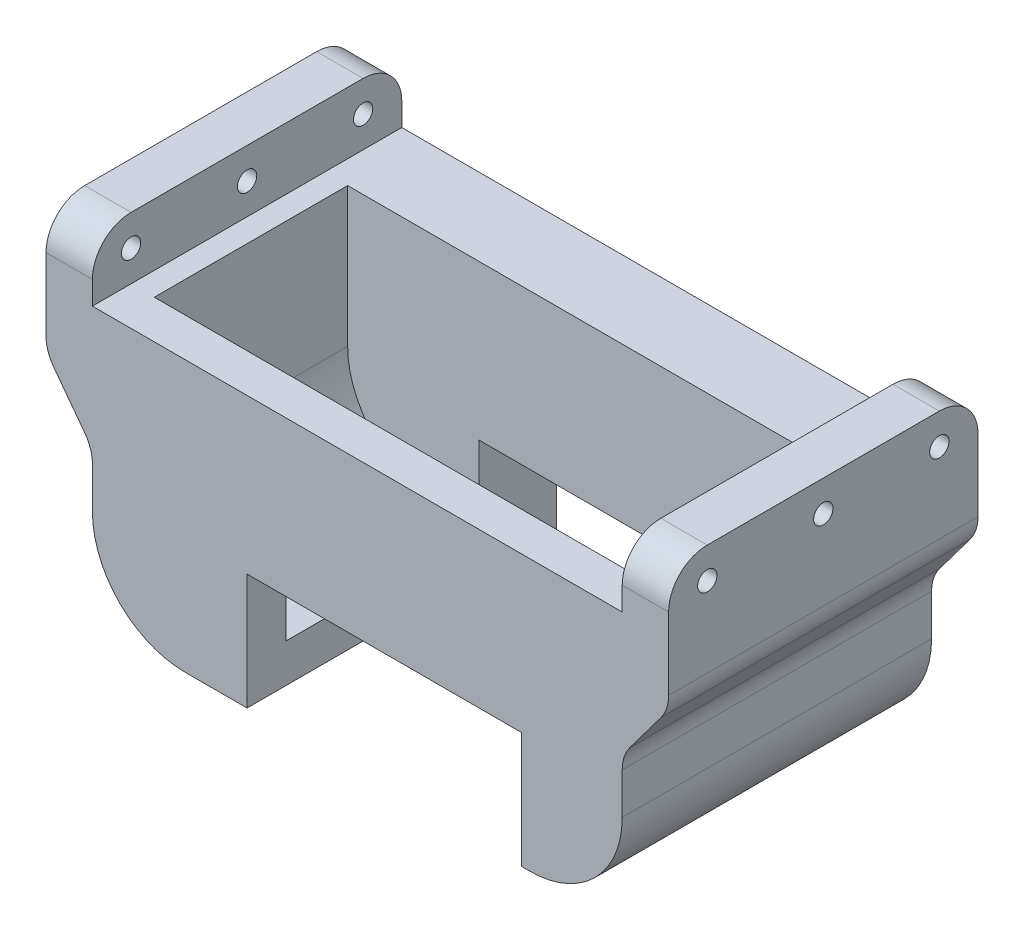
SolidWorks part; units mm, degrees
ref_plane "Front Plane" through (0, 0, 0) normal (0, 0, 1) x (1, 0, 0)
ref_plane "Top Plane" through (0, 0, 0) normal (0, 1, 0) x (1, 0, 0)
ref_plane "Right Plane" through (0, 0, 0) normal (1, 0, 0) x (0, 0, -1)
sketch "Sketch1" plane through (0, 0, 0) normal (0, 0, 1) x (1, 0, 0)
  line L0 (-34.25, 0) -> (34.25, 0)
  line L1 (-34.25, 0) -> (-34.25, -35)
  line L2 (34.25, 0) -> (34.25, -35)
  line L3 (-34.25, -35) -> (-14.25, -35)
  line L4 (34.25, -35) -> (21.25, -35)
  line L5 (-14.25, -35) -> (-14.25, -20)
  line L6 (-14.25, -20) -> (21.25, -20)
  line L7 (21.25, -20) -> (21.25, -35)
  line L8 (-34.25, 0) -> (-34.25, 8)
  line L9 (-34.25, 8) -> (-40.25, 8)
  line L10 (-40.25, 8) -> (-40.25, -8)
  line L11 (34.25, 0) -> (34.25, 8)
  line L12 (34.25, 8) -> (40.25, 8)
  line L13 (40.25, 8) -> (40.25, -8)
  line L14 (-40.25, -8) -> (-34.25, -16)
  line L15 (40.25, -8) -> (34.25, -16)
  point P0 (-37.25, 8)
  point P4 (0, 0)
  dimension "D1" = 68.5
  dimension "D2" = 35
  dimension "D3" = 35
  dimension "D4" = 20
  dimension "D5" = 13
  dimension "D6" = 20
  dimension "D7" = 8
  dimension "D8" = 8
  dimension "D9" = 6
  dimension "D10" = 6
  dimension "D11" = 8
  dimension "D12" = 8
  dimension "D13" = 8
  dimension "D14" = 8
extrude "Boss-Extrude1" add sketch "Sketch1" along normal blind 40 contours L6 L7 L4 L2 L0 L1 L3 L5 | L10 L14 L1 L8 L9 | L15 L13 L12 L11 L2 region at (-0.9993, -14.6448, 0) region at (-37.05, -2.1333, 0) region at (37.05, -2.1333, 0)
sketch "Sketch2" plane through (0, 0, 0) normal (0, 1, 0) x (1, 0, 0)
  line L0 (-14.25, -40) -> (-14.25, 0) construction
  line L1 (-14.25, -35) -> (21.25, -35)
  line L2 (-14.25, -35) -> (-14.25, -10)
  line L3 (-14.25, -10) -> (21.25, -10)
  line L4 (21.25, -35) -> (21.25, -10)
  line L5 (21.25, -40) -> (21.25, 0) construction
  line L9 (-34.25, -40) -> (34.25, -40) construction
  line L10 (-34.25, 0) -> (34.25, 0) construction
  dimension "D1" = 5
  dimension "D2" = 10
extrude "Cut-Extrude1" cut sketch "Sketch2" against normal blind 40
sketch "Sketch3" plane through (0, 0, 0) normal (1, 0, 0) x (0, 0, -1)
  line L0 (-40, 8) -> (-40, -8) construction
  line L1 (-40, 8) -> (0, 8) construction
  line L2 (0, 8) -> (0, -8) construction
  circle A0 centre (-35, 4) radius 1.25
  circle A1 centre (-5, 4) radius 1.25
  circle A2 centre (-20, 4) radius 1.25
  dimension "D1" = 2.5
  dimension "D5" = 2.5
  dimension "D8" = 2.5
  dimension "D2" = 5
  dimension "D3" = 4
  dimension "D4" = 5
  dimension "D6" = 4
  dimension "D7" = 4
  dimension "D9" = 15
extrude "Cut-Extrude2" cut sketch "Sketch3" against normal through all and the other way through all
fillet "Fillet2" radius 5 8 edges at (-34.25, -16, 20) (-40.25, -8, 20) (40.25, -8, 20) (34.25, -16, 20) (37.25, 8, 0) (-37.25, 8, 0) (37.25, 8, 40) (-37.25, 8, 40)
chamfer "Chamfer1" distance 5 angle 45 1 edges at (21.25, -27.5, 0)
sketch "Sketch4" plane through (0, 0, 0) normal (0, 1, 0) x (1, 0, 0)
  line L0 (-14.25, -35) -> (21.25, -35) construction
  line L1 (-14.25, -10) -> (-31.25, -10)
  line L2 (-14.25, -10) -> (-14.25, -35)
  line L3 (-14.25, -35) -> (-31.25, -35)
  line L4 (-31.25, -10) -> (-31.25, -35)
  line L5 (21.25, -10) -> (31.25, -10)
  line L6 (21.25, -10) -> (21.25, -35)
  line L7 (21.25, -35) -> (31.25, -35)
  line L8 (31.25, -10) -> (31.25, -35)
  line L9 (21.25, -35) -> (21.25, -10) construction
  line L10 (34.25, -40) -> (34.25, 0) construction
  line L11 (-34.25, -40) -> (-34.25, 0) construction
  point P10 (-14.25, -35)
  point P12 (21.25, -35)
  dimension "D1" = 3
  dimension "D2" = 3
extrude "Cut-Extrude3" cut sketch "Sketch4" against normal blind 30
fillet "Fillet3" radius 12 4 edges at (-34.25, -35, 20) (34.25, -35, 20) (31.25, -30, 22.5) (-31.25, -30, 22.5)
